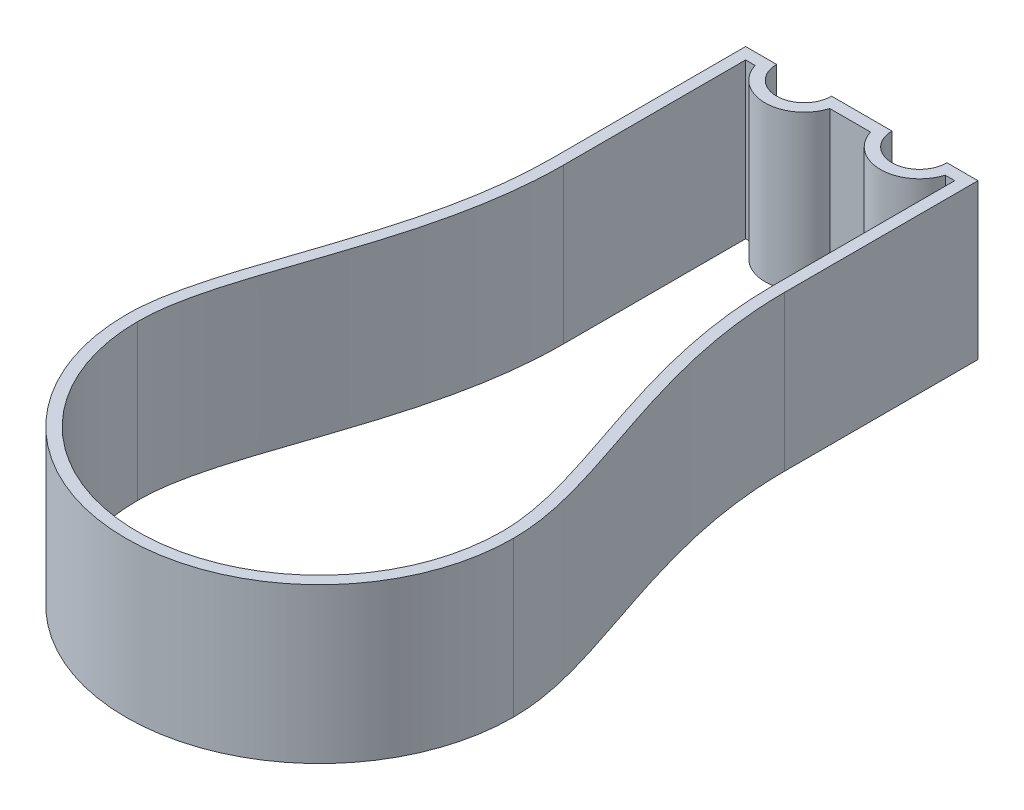
SolidWorks part; units mm, degrees
material "3.1355 (EN-AW 2024)"
ref_plane "Front" through (0, 0, 0) normal (0, 0, 1) x (1, 0, 0)
ref_plane "Top" through (0, 0, 0) normal (0, 1, 0) x (1, 0, 0)
ref_plane "Right" through (0, 0, 0) normal (1, 0, 0) x (0, 0, -1)
sketch "Эскиз1" plane through (0, 0, 0) normal (0, 1, 0) x (1, 0, 0)
  line L0 (0, 0) -> (8, 0)
  line L1 (0, 0) -> (0, -100) construction
  line L2 (0, -12.5175) -> (60, -12.5175) construction
  line L3 (8, 0) -> (22.2, 0) construction
  line L4 (30, -12.5175) -> (30, 0) construction
  line L5 (60, 0) -> (52, 0)
  line L6 (60, 0) -> (60, -100) construction
  line L7 (22.2, 0) -> (37.8, 0)
  line L8 (30, 0) -> (30, -140) construction
  line L9 (0, -80.7644) -> (0, -19.2352) construction
  line L10 (0, 0) -> (0, -50)
  line L11 (60, 0) -> (60, -50)
  arc A0 (22.2, 0) -> (8, 0) centre (15.1, 0) cw
  arc A1 (37.8, 0) -> (52, 0) centre (44.9, 0) ccw
  circle A2 centre (30, -140) radius 47 construction
  circle A3 centre (30, -140) radius 50 construction
  arc A4 (-20, -140) -> (80, -140) centre (30, -140) ccw
  spline S0 degree 3 poles (0, -50) (0, -86.1164) (-20.1607, -116.6426) (-20, -140) knots 0 0 0 0 1 1 1 1
  spline S1 degree 3 poles (60, -50) (60, -86.1164) (80.1607, -116.6426) (80, -140) knots 0 0 0 0 1 1 1 1
  dimension "D3" = 7.1
  dimension "D5" = 94
  dimension "D6" = 100
  dimension "D1" = 60
  dimension "D2" = 8
  dimension "D4" = 140
extrude "Бобышка-Вытянуть1" add sketch "Эскиз1" along normal blind 40
sketch "Эскиз2" plane through (0, 0, 0) normal (0, -1, 0) x (1, 0, 0)
  line L10 (3, 50) -> (3, 3)
  line L11 (3, 3) -> (5.4558, 3)
  line L12 (24.7442, 3) -> (35.2558, 3)
  line L13 (54.5442, 3) -> (57, 3)
  line L14 (57, 3) -> (57, 50)
  line L15 (0, 50) -> (0, 0)
  line L16 (60, 0) -> (60, 50)
  line L17 (52, 0) -> (60, 0)
  line L18 (22.2, 0) -> (37.8, 0)
  line L19 (0, 0) -> (8, 0)
  line L20 (0, 50) -> (0, 0) construction
  line L21 (60, 0) -> (60, 50) construction
  line L22 (52, 0) -> (60, 0) construction
  line L23 (22.2, 0) -> (37.8, 0) construction
  line L24 (0, 0) -> (8, 0) construction
  arc A6 (24.7442, 3) -> (5.4558, 3) centre (15.1, 0) ccw
  arc A7 (54.5442, 3) -> (35.2558, 3) centre (44.9, 0) ccw
  arc A8 (77, 139.9898) -> (-17, 139.9898) centre (30, 140) ccw
  arc A9 (80, 140) -> (-20, 140) centre (30, 140) ccw
  arc A10 (52, 0) -> (37.8, 0) centre (44.9, 0) ccw
  arc A11 (22.2, 0) -> (8, 0) centre (15.1, 0) ccw
  arc A12 (80, 140) -> (-20, 140) centre (30, 140) ccw construction
  arc A13 (52, 0) -> (37.8, 0) centre (44.9, 0) ccw construction
  arc A14 (22.2, 0) -> (8, 0) centre (15.1, 0) ccw construction
  spline S4 degree 1 poles (57, 50) (77, 139.9898) knots 0 0 1 1 construction
  spline S5 degree 1 poles (-17, 139.9898) (3, 50) knots 0 0 1 1 construction
  spline S6 degree 3 poles (2974.8733, 17.0098) (-3143.323, 462.9237) (3099.91, -31.1134) (-2928.364, -504.442) knots -3.750439 -3.750439 -3.750439 -3.750439 4.723475 4.723475 4.723475 4.723475 only from (-20, 140) to (0, 50)
  spline S7 degree 3 poles (2988.4431, -504.4482) (-3039.9457, -31.1192) (3203.3107, 462.9225) (-2914.8159, 17.014) knots -3.723512 -3.723512 -3.723512 -3.723512 4.750412 4.750412 4.750412 4.750412 only from (60, 50) to (80, 140)
  spline S8 degree 3 poles (-20, 140) (-20.1607, 116.6426) (0, 86.1164) (0, 50) knots 0 0 0 0 1 1 1 1 construction
  spline S9 degree 3 poles (60, 50) (60, 86.1164) (80.1607, 116.6426) (80, 140) knots 0 0 0 0 1 1 1 1 construction
  spline S10 degree 3 poles (57, 50) (57, 51.1576) (57.0406, 53.4814) (57.2737, 58.0563) (57.83, 63.6856) (58.8582, 70.2787) (60.6258, 78.8545) (63.4224, 89.1625) (67.2233, 100.8564) (70.9826, 111.8507) (73.6803, 120.399) (75.3443, 126.8384) (76.2901, 131.4596) (76.7833, 135.1228) (76.9778, 137.9476) (77.0047, 139.3043) (77, 139.9898) knots 0 0 0 0 0.031255 0.062509 0.125019 0.187528 0.250037 0.375056 0.500075 0.625093 0.750112 0.812622 0.875131 0.93764 0.968895 1.00015 1.00015 1.00015 1.00015
  spline S11 degree 3 poles (-17, 139.9898) (-17.0047, 139.3043) (-16.9778, 137.9476) (-16.7833, 135.1228) (-16.2901, 131.4596) (-15.3443, 126.8384) (-13.6803, 120.399) (-10.9826, 111.8507) (-7.2233, 100.8564) (-3.4224, 89.1625) (-0.6258, 78.8545) (1.1418, 70.2787) (2.17, 63.6856) (2.7263, 58.0563) (2.9594, 53.4814) (3, 51.1576) (3, 50) knots -0.00015 -0.00015 -0.00015 -0.00015 0.031105 0.06236 0.124869 0.187378 0.249888 0.374907 0.499925 0.624944 0.749963 0.812472 0.874981 0.937491 0.968745 1 1 1 1
  dimension "D1" = 0
  dimension "D2" = 3
extrude "Вырез-Вытянуть1" cut sketch "Эскиз2" against normal through all
